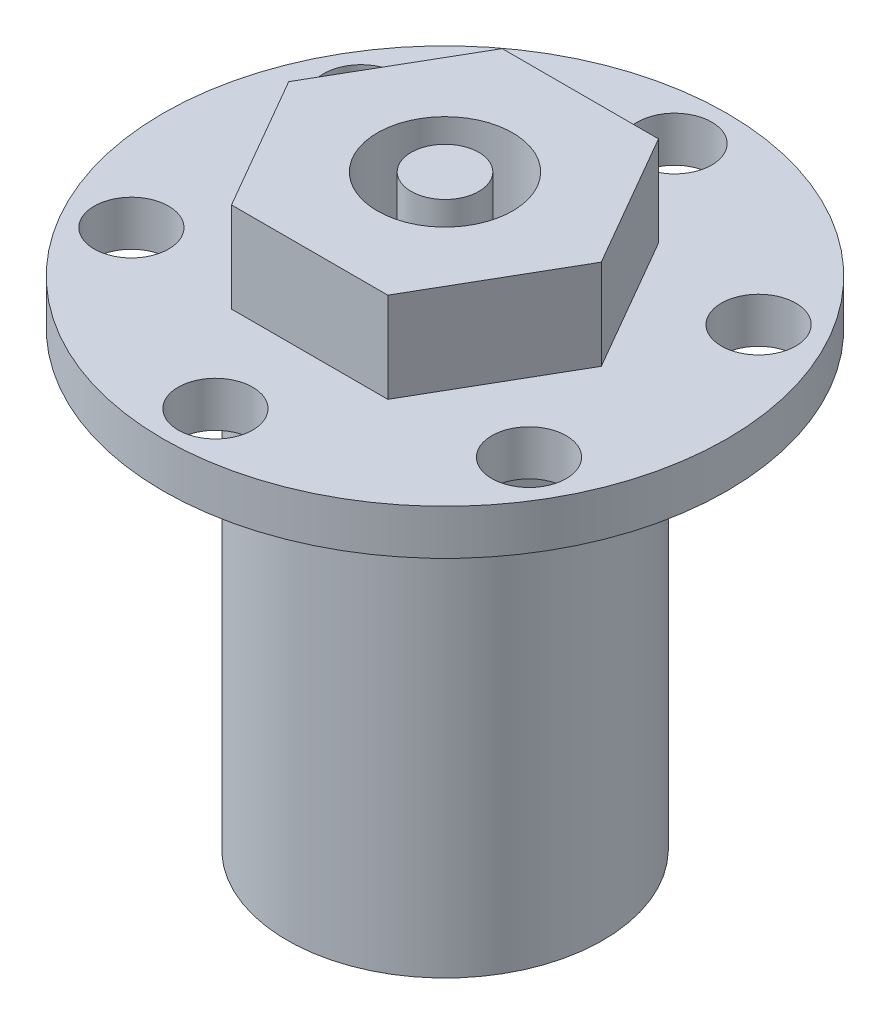
SolidWorks part; units mm, degrees
ref_plane "Спереди" through (0, 0, 0) normal (0, 0, 1) x (1, 0, 0)
ref_plane "Сверху" through (0, 0, 0) normal (0, 1, 0) x (1, 0, 0)
ref_plane "Справа" through (0, 0, 0) normal (1, 0, 0) x (0, 0, -1)
sketch "Эскиз1" plane through (0, 0, 0) normal (0, 1, 0) x (1, 0, 0)
  circle A0 centre (0, 0) radius 12.5
extrude "Бобышка-Вытянуть1" add sketch "Эскиз1" along normal blind 2
sketch "Эскиз2" plane through (0, 0, 0) normal (0, -1, 0) x (1, 0, 0)
  circle A0 centre (0, -10.1761) radius 1.65
extrude "Вырез-Вытянуть1" cut sketch "Эскиз2" against normal through all
pattern_circular "Круговой массив1" count 6 over 360 about axis through (0, 2, 0) along (0, 1, 0) of "Вырез-Вытянуть1"
sketch "Эскиз3" plane through (0, 0, 0) normal (0, -1, 0) x (1, 0, 0)
  circle A0 centre (0, 0) radius 7
extrude "Бобышка-Вытянуть2" add sketch "Эскиз3" along normal blind 20
sketch "Эскиз4" plane through (0, 2, 0) normal (0, 1, 0) x (1, 0, 0)
  line L1 (-6.9282, 0) -> (-3.4641, -6)
  line L2 (-3.4641, -6) -> (3.4641, -6)
  line L3 (3.4641, -6) -> (6.9282, 0)
  line L4 (6.9282, 0) -> (3.4641, 6)
  line L5 (3.4641, 6) -> (-3.4641, 6)
  line L6 (-3.4641, 6) -> (-6.9282, 0)
  circle A0 centre (0, 0) radius 6 construction
extrude "Бобышка-Вытянуть3" add sketch "Эскиз4" along normal blind 4
sketch "Эскиз5" plane through (0, 6, 0) normal (0, 1, 0) x (1, 0, 0)
  circle A0 centre (0, 0) radius 3
  circle A1 centre (0, 0) radius 1.5
  dimension "D1" = 6
  dimension "D2" = 3
extrude "Вырез-Вытянуть2" cut sketch "Эскиз5" against normal up to surface (4 mm away) up to face at (0, 2, 0)
